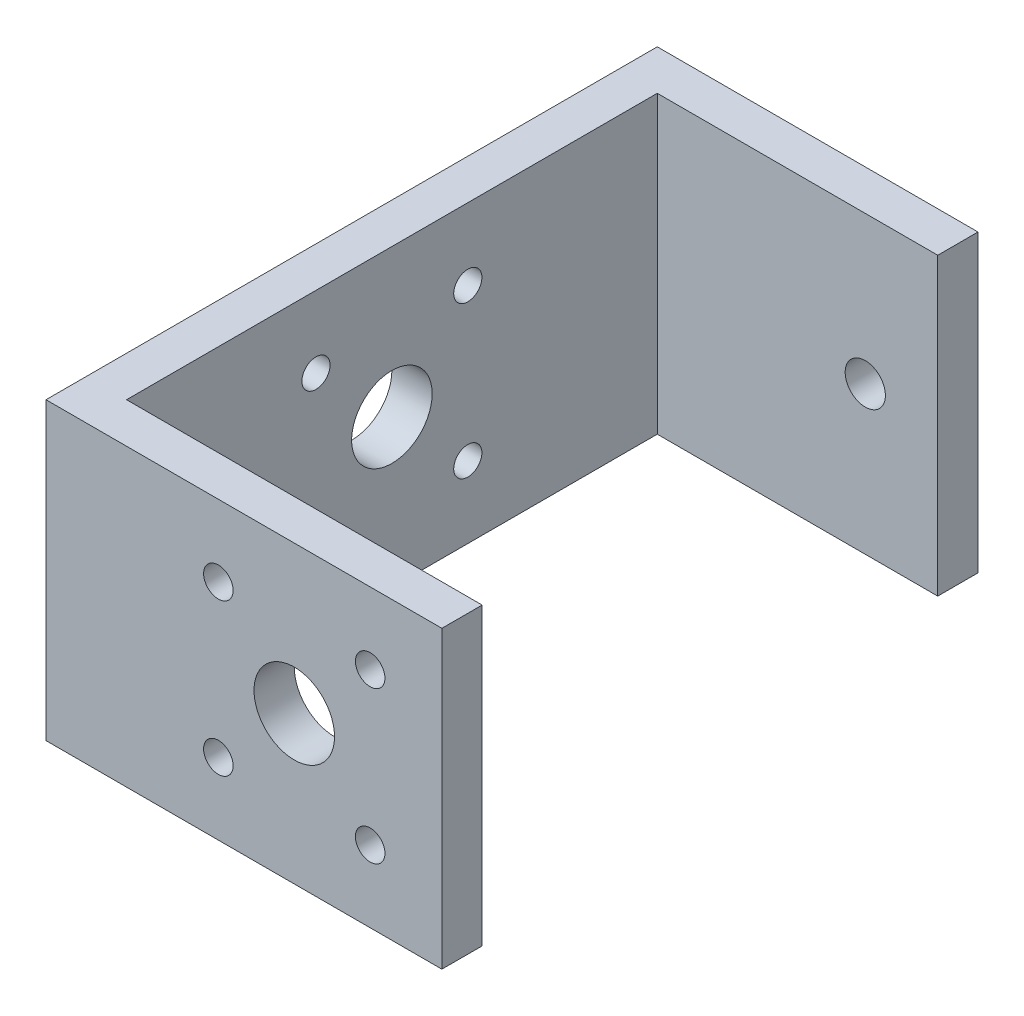
SolidWorks part; units mm, degrees
ref_plane "Front Plane" through (0, 0, 0) normal (0, 0, 1) x (1, 0, 0)
ref_plane "Top Plane" through (0, 0, 0) normal (0, 1, 0) x (1, 0, 0)
ref_plane "Right Plane" through (0, 0, 0) normal (1, 0, 0) x (0, 0, -1)
sketch "Sketch1" plane through (0, 0, 0) normal (1, 0, 0) x (0, 0, -1)
  line L0 (-14, 0) -> (-11, 0) construction
  line L1 (5.6569, 5.6569) -> (0, 0) construction
  line L2 (-19.775, 11) -> (-19.775, -11)
  line L3 (-22.775, 11) -> (22.775, 11)
  line L4 (-22.775, 11) -> (-22.775, -11)
  line L5 (-22.775, -11) -> (22.775, -11)
  line L6 (22.775, 11) -> (22.775, -11)
  line L7 (-22.775, 11) -> (22.775, -11) construction
  line L8 (-22.775, -11) -> (22.775, 11) construction
  line L10 (0, 12.1) -> (0, -12.1) construction
  line L11 (19.775, 11) -> (19.775, -11)
  line L12 (-3, 0) -> (14, 0) construction
  circle A1 centre (5.6569, 5.6569) radius 1.05
  circle A2 centre (0, 0) radius 3
  circle A3 centre (5.6569, -5.6569) radius 1.05
  circle A4 centre (-5.6569, -5.6569) radius 1.05
  circle A5 centre (-5.6569, 5.6569) radius 1.05
  dimension "D1" = 45.55
  dimension "D2" = 8
  dimension "D4" = 2.1
  dimension "D5" = 6
  dimension "D3" = 45
  dimension "D7" = 22
  dimension "D8" = 3
  dimension "D6" = 4
extrude "Boss-Extrude1" add sketch "Sketch1" along normal blind 3 contours L3 L5 A5 A4 A3 A2 A1 region at (0, 10.5474, 0)
extrude "Boss-Extrude2" add sketch "Sketch1<6>" along normal blind 29.5 contours L4 L5 L2 L3 region at (0, 0, 21.275)
sketch "Sketch1<6>" plane through (0, 0, 0) normal (1, 0, 0) x (0, 0, -1) same geometry as "Sketch1"
extrude "Boss-Extrude3" add sketch "Sketch1<7>" along normal blind 23.9 contours L3 L11 L5 L6 region at (0, 0, -21.275)
sketch "Sketch1<7>" plane through (0, 0, 0) normal (1, 0, 0) x (0, 0, -1) same geometry as "Sketch1"
sketch "Sketch2" plane through (0, 0, 22.775) normal (0, 0, 1) x (1, 0, 0)
  line L0 (29.5, 11) -> (7.5, -11) construction
  line L1 (29.5, -11) -> (0, -11) construction
  line L2 (29.5, -11) -> (7.5, 11) construction
  line L3 (29.5, 11) -> (0, 11) construction
  circle A0 centre (18.5, 0) radius 3
  circle A1 centre (24.1569, 5.6569) radius 1.1
  dimension "D2" = 6
  dimension "D4" = 2.2
  dimension "D1" = 22
  dimension "D3" = 8
extrude "Cut-Extrude1" cut sketch "Sketch2" against normal up to surface (3 mm away) up to face at (16.25, 0, 19.775)
pattern_circular "CirPattern1" count 4 over 360 about axis through (18.5, 0, 22.775) along (0, 0, 1) of "Cut-Extrude1"
sketch "Sketch3" plane through (0, 0, -22.775) normal (0, 0, -1) x (-1, 0, 0)
  circle A0 centre (-18.5, 0) radius 1.5
  dimension "D1" = 3
extrude "Cut-Extrude2" cut sketch "Sketch3" against normal up to surface (3 mm away) up to face at (13.45, 0, -19.775)
move or copy body "Body-Move/Copy1" [suppressed] bodies to move or copy 117
